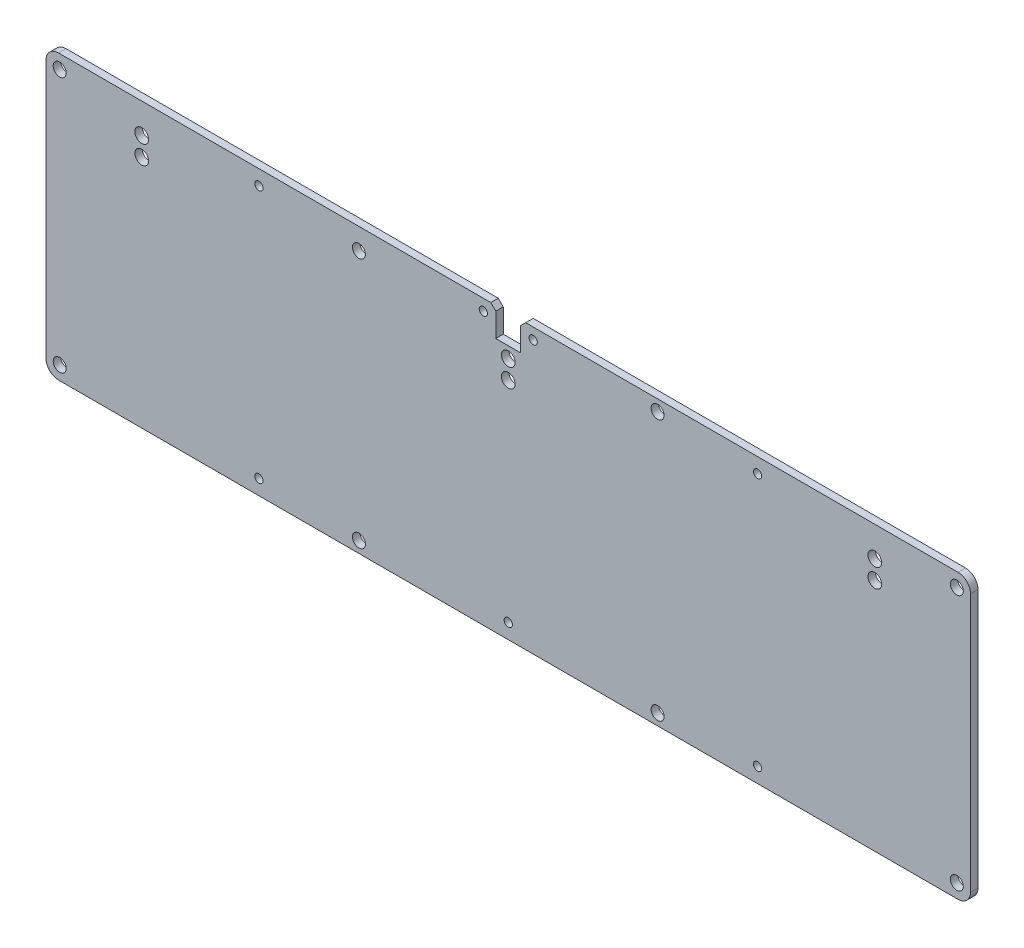
SolidWorks part; units mm, degrees
ref_plane "Front Plane" through (0, 0, 0) normal (0, 0, 1) x (1, 0, 0)
ref_plane "Top Plane" through (0, 0, 0) normal (0, 1, 0) x (1, 0, 0)
ref_plane "Right Plane" through (0, 0, 0) normal (1, 0, 0) x (0, 0, -1)
sketch "Model" plane through (0, 0, 0) normal (0, 0, 1) x (1, 0, 0)
  line L0 (0, 108.6) -> (0, 5)
  line L1 (365.775, 0) -> (5, 0)
  line L2 (370.775, 108.6) -> (370.775, 5)
  line L3 (180.3875, 111.6) -> (178.3875, 113.6)
  line L4 (5, 113.6) -> (178.3875, 113.6)
  line L5 (180.3875, 111.6) -> (180.3875, 102.1)
  line L6 (180.3875, 102.1) -> (190.3875, 102.1)
  line L7 (190.3875, 111.6) -> (192.3875, 113.6)
  line L8 (190.3875, 111.6) -> (190.3875, 102.1)
  line L9 (192.3875, 113.6) -> (365.775, 113.6)
  arc A0 (365.775, 0) -> (370.775, 5) centre (365.775, 5) ccw
  arc A1 (370.775, 108.6) -> (365.775, 113.6) centre (365.775, 108.6) ccw
  arc A2 (0, 5) -> (5, 0) centre (5, 5) ccw
  circle A3 centre (5.5, 108.1) radius 2.6
  circle A4 centre (5.5, 5.5) radius 2.6
  circle A5 centre (365.275, 5.5) radius 2.6
  circle A6 centre (365.275, 108.1) radius 2.6
  arc A7 (5, 113.6) -> (0, 108.6) centre (5, 108.6) ccw
  circle A8 centre (125.5, 4.5) radius 2.6
  circle A9 centre (195.3875, 109.1) radius 1.65
  circle A10 centre (175.3875, 109.1) radius 1.65
  circle A11 centre (38.3875, 94.1) radius 2.75
  circle A12 centre (38.3875, 101.6) radius 2.75
  circle A13 centre (332.3875, 94.1) radius 2.75
  circle A14 centre (332.3875, 101.6) radius 2.75
  circle A15 centre (185.3875, 90.1) radius 2.75
  circle A16 centre (185.3875, 97.6) radius 2.75
  circle A17 centre (85.3875, 107.6) radius 1.65
  circle A18 centre (285.3875, 107.6) radius 1.65
  circle A19 centre (85.3875, 6) radius 1.65
  circle A20 centre (185.3875, 6) radius 1.65
  circle A21 centre (285.3875, 6) radius 1.65
  circle A22 centre (245.275, 4.5) radius 2.6
  circle A23 centre (125.5, 105.1) radius 2.6
  circle A24 centre (245.275, 109.1) radius 2.6
  point P60 (180.3875, 106.85)
  point P61 (0, 0)
  dimension "D2" = 3.3
  dimension "D3" = 3.3
  dimension "D4" = 3.3
  dimension "D5" = 3.3
  dimension "D6" = 3.3
  dimension "D7" = 3.3
  dimension "D8" = 3.3
  dimension "D20" = 5.2
  dimension "D21" = 5.5
  dimension "D1" = 113.6
  dimension "D9" = 5.5
  dimension "D10" = 5.5
  dimension "D11" = 10
  dimension "D14" = 7.5
  dimension "D15" = 11.5
  dimension "D12" = 59.8875
  dimension "D16" = 38.3875
  dimension "D17" = 85.3875
  dimension "D18" = 120
  dimension "D19" = 119.775
  dimension "D13" = 4.5
  dimension "D22" = 6
  dimension "D23" = 8.5
extrude "Boss-Extrude1" add sketch "Model" along normal blind 3
equation "\"A\"= 3.3"
equation "\"D2@Model\"=\"A\""
equation "\"D3@Model\"=\"A\""
equation "\"D4@Model\"=\"A\""
equation "\"D5@Model\"=\"A\""
equation "\"D6@Model\"=\"A\""
equation "\"D7@Model\"=\"A\""
equation "\"D8@Model\"=\"A\""
